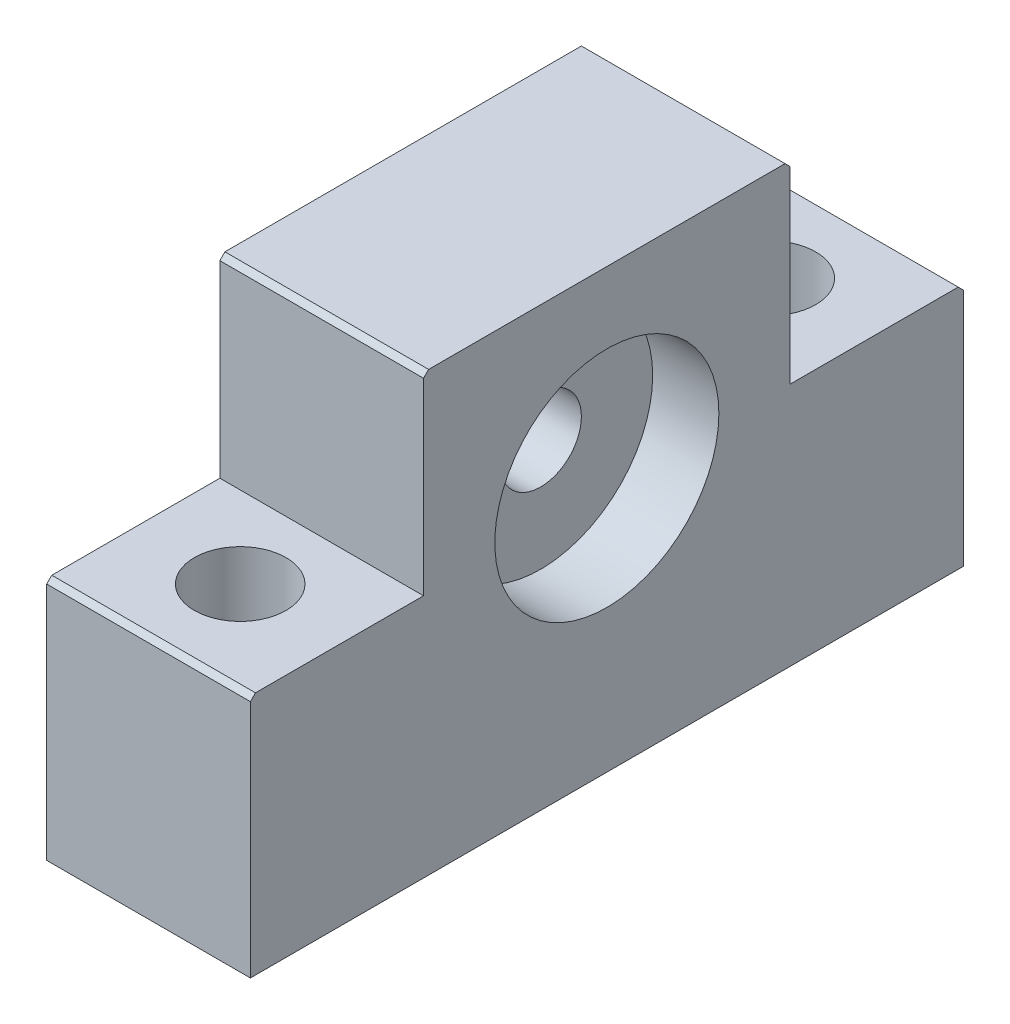
SolidWorks part; units mm, degrees
note: '?' marks a value the reader was unsure of.
ref_plane "Front Plane" through (0, 0, 0) normal (0, 0, 1) x (1, 0, 0)
ref_plane "Top Plane" through (0, 0, 0) normal (0, 1, 0) x (1, 0, 0)
ref_plane "Right Plane" through (0, 0, 0) normal (1, 0, 0) x (0, 0, -1)
ref_axis "Axis_X" through (-1, 0, 0) along (1, 0, 0)?
ref_axis "Axis_Y" through (0, 45.15, 0) along (0, -1, 0)?
ref_axis "Axis_Z" through (0, 0, -38.5) along (0, 0, 1)?
sketch "Sketch1" plane through (0, 0, 0) normal (1, 0, 0) x (0, 0, -1)
  line L0 (-18, 42.5) -> (-18, 24)
  line L1 (-17.5, 43) -> (17.5, 43)
  line L2 (-35, 23.5) -> (-35, 0)
  line L3 (-35, 0) -> (35, 0)
  line L4 (35, 23.5) -> (35, 0)
  line L5 (-34.5, 24) -> (-35, 23.5)
  line L6 (34.5, 24) -> (35, 23.5)
  line L7 (-18, 24) -> (-34.5, 24)
  line L8 (18, 42.5) -> (18, 24)
  line L9 (18, 24) -> (34.5, 24)
  line L10 (-18, 42.5) -> (-17.5, 43)
  line L11 (17.5, 43) -> (18, 42.5)
  dimension "B" = 70
  dimension "H" = 43
  dimension "H1" = 24
  dimension "B1" = 36
  dimension "FIX_41" = 45
  dimension "FIX_42" = 0.5
extrude "Boss-Extrude1" add sketch "Sketch1" along normal blind 20
hole_wizard "CBORE1" [suppressed] positions "Sketch3" profile "Sketch2" counterbore size "M4" standard "JIS"
sketch "Sketch3" plane through (0, 20, 0) normal (0, 1, 0) x (1, 0, 0)
  line L0 (6, 15) -> (6, -15) construction
  line L1 (6, 0) -> (0, 0) construction
  point P0 (6, 15)
  point P2 (6, -15)
  dimension "P" = 52
  dimension "KSS_1" = 10
sketch "Sketch2" plane through (6, 20, -15) normal (1, 0, 0) x (0, 0, 1)
  line L0 (0, 0) -> (0, 20)
  line L1 (0, 20) -> (2.75, 20)
  line L3 (2.75, 20) -> (2.75, 11)
  line L4 (2.75, 11) -> (4.75, 11)
  line L5 (4.75, 11) -> (4.75, 0)
  line L7 (4.75, 0) -> (0, 0)
  line L11 (0, -6.35) -> (0, 107.95) construction
  dimension "D1_s" = 9
  dimension "Thru Hole Depth" = 20
  dimension "D2_s" = 9.5
  dimension "L_s" = 11
sketch "Sketch4" plane through (0, 0, 0) normal (0, 0, 1) x (1, 0, 0)
  line L0 (0, 36) -> (6.5, 36)
  line L1 (6.5, 36) -> (6.5, 29)
  line L2 (6.5, 29) -> (13.5, 29)
  line L3 (13.5, 29) -> (13.5, 36)
  line L4 (13.5, 36) -> (20, 36)
  line L5 (20, 36) -> (20, 25)
  line L6 (0, 36) -> (0, 25)
  line L7 (20, 25) -> (0, 25)
  line L10 (20, 25) -> (0, 25) construction
  dimension "V" = 22
  dimension "D_s" = 8
  dimension "MSM_51" = 6.5
  dimension "L" = 20
  dimension "H_S" = 25
revolve "Cut-Revolve1" cut sketch "Sketch4" angle 360 about L10
hole_wizard "DiameterHole1" positions "Sketch6" profile "Sketch5" hole size "Ø0.15" standard "JIS" end condition through all
sketch "Sketch6" plane through (0, 24, 0) normal (0, 1, 0) x (1, 0, 0)
  line L0 (10, -26) -> (10, 26) construction
  line L2 (0, 0) -> (10, 0) construction
  point P0 (10, -26)
  point P3 (10, 26)
  dimension "P" = 52
  dimension "KSS_1" = 10
sketch "Sketch5" plane through (10, 24, 26) normal (1, 0, 0) x (0, 0, 1)
  line L0 (0, 0) -> (0, 24)
  line L1 (0, 24) -> (4.5, 24)
  line L2 (4.5, 24) -> (4.5, 0)
  line L5 (4.5, 0) -> (0, 0)
  line L11 (0, -6.35) -> (0, 107.95) construction
  dimension "D1_s" = 9
  dimension "Thru Hole Depth" = 24
equation "\"Factor\"= 1.082532"
equation "\"KSS_1\"= \"L@Boss-Extrude1\" / 2"
